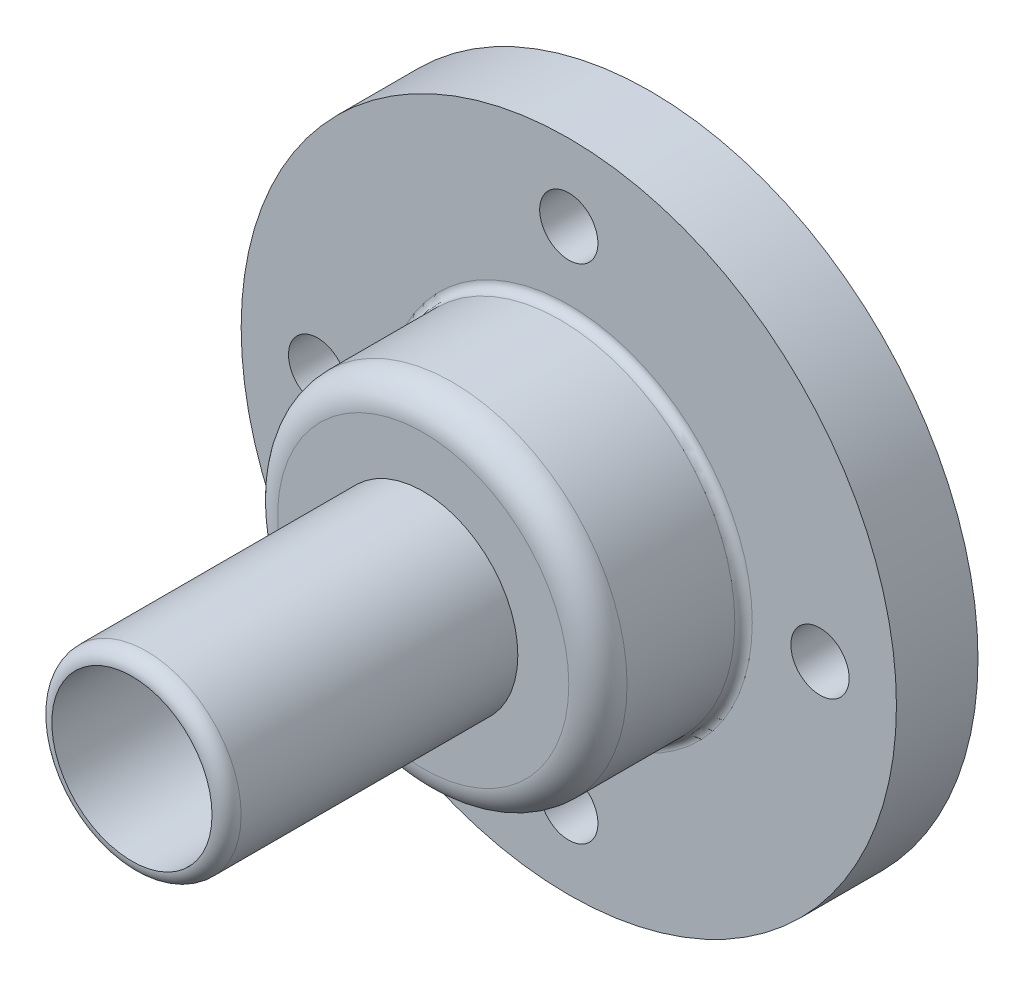
SolidWorks part; units mm, degrees
ref_plane "Front Plane" through (0, 0, 0) normal (0, 0, 1) x (1, 0, 0)
ref_plane "Top Plane" through (0, 0, 0) normal (0, 1, 0) x (1, 0, 0)
ref_plane "Right Plane" through (0, 0, 0) normal (1, 0, 0) x (0, 0, -1)
sketch "Sketch2" plane through (0, 0, 0) normal (0, 0, 1) x (1, 0, 0)
  circle A0 centre (0, 0) radius 112.5
extrude "Boss-Extrude1" add sketch "Sketch2" along normal blind 28
sketch "Sketch4" plane through (0, 0, 28) normal (0, 0, 1) x (1, 0, 0)
  circle A0 centre (0, 0) radius 60
extrude "Boss-Extrude5" add sketch "Sketch4" along normal blind 50 contours A0
fillet "Fillet2" radius 3 1 edges at (60, 0, 28)
fillet "Fillet3" radius 10 1 edges at (60, 0, 78)
sketch "Sketch7" plane through (0, 0, 78) normal (0, 0, 1) x (1, 0, 0)
  circle A0 centre (0, 0) radius 32.5
extrude "Boss-Extrude7" add sketch "Sketch7" along normal blind 100 contours A0
sketch "Sketch8" plane through (0, 0, 178) normal (0, 0, 1) x (1, 0, 0)
  circle A0 centre (0, 0) radius 27.5
extrude "Cut-Extrude1" cut sketch "Sketch8" against normal through all contours A0
sketch "Sketch9" plane through (0, 0, 28) normal (0, 0, 1) x (1, 0, 0)
  circle A0 centre (0, 86.25) radius 10
  circle A1 centre (86.25, 0) radius 10
  circle A2 centre (0, -86.25) radius 10
  circle A3 centre (-86.25, 0) radius 10
  dimension "D1" = 4
extrude "Cut-Extrude2" cut sketch "Sketch9" against normal through all
fillet "Fillet4" radius 5 1 edges at (32.5, 0, 178)
